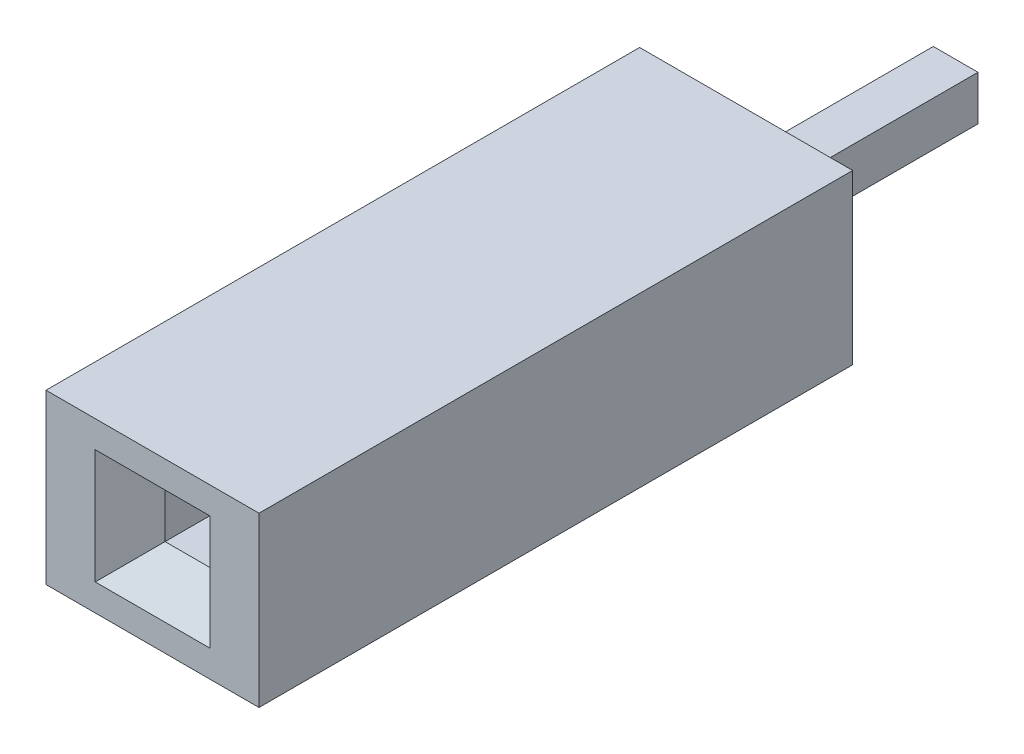
SolidWorks part; units mm, degrees
ref_plane "Front Plane" through (0, 0, 0) normal (0, 0, 1) x (1, 0, 0)
ref_plane "Top Plane" through (0, 0, 0) normal (0, 1, 0) x (1, 0, 0)
ref_plane "Right Plane" through (0, 0, 0) normal (1, 0, 0) x (0, 0, -1)
sketch "Sketch1" plane through (0, 0, 0) normal (0, 0, 1) x (1, 0, 0)
  line L1 (-1.525, 1.205) -> (1.525, 1.205)
  line L2 (-1.525, 1.205) -> (-1.525, -1.205)
  line L3 (-1.525, -1.205) -> (1.525, -1.205)
  line L4 (1.525, 1.205) -> (1.525, -1.205)
  line L9 (-0.32, 0.32) -> (0.32, 0.32)
  line L10 (-0.32, 0.32) -> (-0.32, -0.32)
  line L11 (-0.32, -0.32) -> (0.32, -0.32)
  line L12 (0.32, 0.32) -> (0.32, -0.32)
  dimension "D1" = 3.05
  dimension "D2" = 2.41
  dimension "D3" = 1.205
  dimension "D4" = 1.525
  dimension "D5" = 0.64
  dimension "D6" = 0.64
  dimension "D7" = 0.32
  dimension "D8" = 0.32
sketch "Sketch2" plane through (0, 0, 0) normal (1, 0, 0) x (0, 0, -1)
  line L0 (0, 0.32) -> (0, -0.32) construction
  line L1 (0, -0.32) -> (1.2, -0.32)
  line L2 (0, -0.32) -> (0, 0.32)
  line L5 (0, 0.32) -> (1.84, 0.32)
  line L7 (1.2, -0.32) -> (1.2, -3.745)
  line L8 (1.2, -3.745) -> (1.84, -3.745)
  line L9 (1.84, 0.32) -> (1.84, -3.745)
  line L11 (0, 0.32) -> (3.2, 0.32)
  line L12 (0, 0.32) -> (0, -0.32)
  line L13 (0, -0.32) -> (3.2, -0.32)
  line L14 (3.2, 0.32) -> (3.2, -0.32)
  dimension "D1" = 1.84
  dimension "D2" = 3.745
  dimension "D3" = 0.64
  dimension "D4" = 0.32
  dimension "D5" = 3.2
  dimension "D6" = 0.64
extrude "Boss-Extrude1" add sketch "Sketch1" along normal blind 8.5 contours L3 L4 L1 L2
extrude "Cut-Extrude1" cut sketch "Sketch1<3>" against normal blind 5 from surface contours L10 L11 L12 L9 starting at face at (0, 0, 8.5)
sketch "Sketch1<3>" plane through (0, 0, 0) normal (0, 0, 1) x (1, 0, 0) same geometry as "Sketch1"
chamfer "Chamfer1" distance 0.5 angle 45 4 edges at (0.32, 0, 8.5) (0, 0.32, 8.5) (-0.32, 0, 8.5) (0, -0.32, 8.5)
extrude "Boss-Extrude2" add sketch "Sketch2" along normal mid plane 0.64 contours L14 L11 L9 L13 | L1 L13 L9 L5 L2 region at (0, 0, -0.92) region at (0, 0, -2.52)
chamfer "Chamfer2" distance 0.2 angle 45 4 edges at (0.32, 0, -3.2) (0, -0.32, -3.2) (-0.32, 0, -3.2) (0, 0.32, -3.2)
ref_point "Point2"
ref_point "Point4"
ref_axis "Axis1" through (0, 0, -3.2) along (0, 0, 1)
